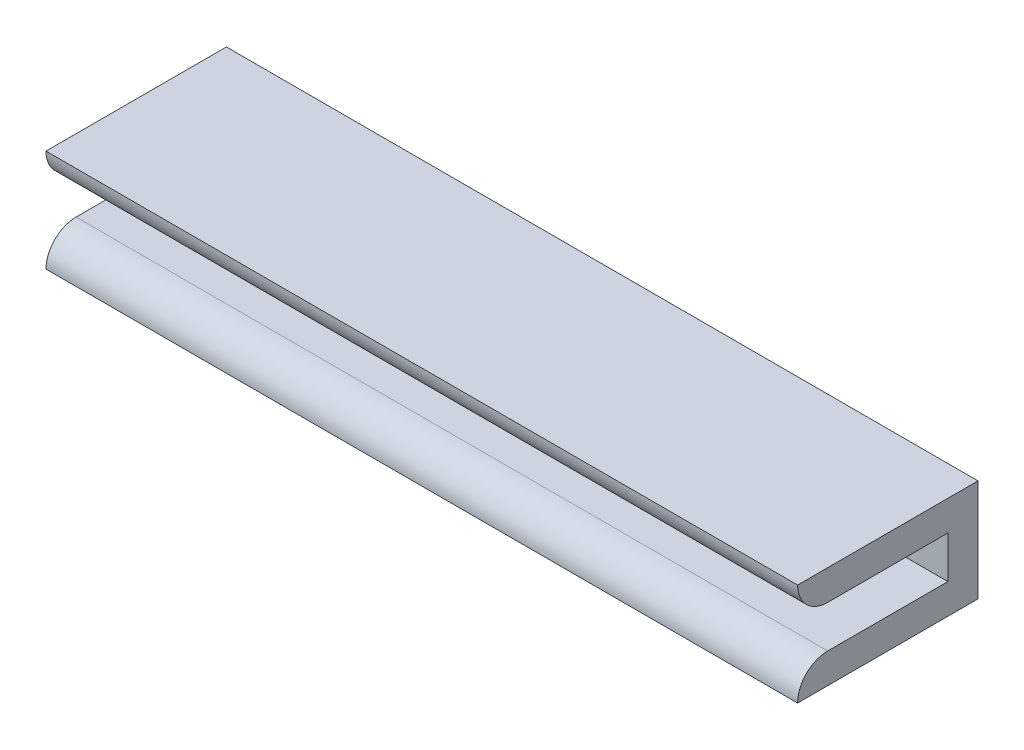
SolidWorks part; units mm, degrees
ref_plane "前视基准面" through (0, 0, 0) normal (0, 0, 1) x (1, 0, 0)
ref_plane "上视基准面" through (0, 0, 0) normal (0, 1, 0) x (1, 0, 0)
ref_plane "右视基准面" through (0, 0, 0) normal (1, 0, 0) x (0, 0, -1)
sketch "草图1" plane through (0, 0, 0) normal (0, 0, 1) x (1, 0, 0)
  line L1 (0, 0) -> (50, 0)
  line L2 (0, 0) -> (0, 2)
  line L3 (0, 2) -> (50, 2)
  line L4 (50, 0) -> (50, 2)
  line L5 (0, -2.8) -> (50, -2.8)
  line L6 (0, -2.8) -> (0, -4.8)
  line L7 (0, -4.8) -> (50, -4.8)
  line L8 (50, -2.8) -> (50, -4.8)
  dimension "D1" = 2
  dimension "D2" = 2
  dimension "D3" = 2.8
  dimension "D4" = 50
extrude "凸台-拉伸1" add sketch "草图1" along normal blind 10
sketch "草图2" plane through (0, 0, 0) normal (0, 0, -1) x (-1, 0, 0)
  line L1 (-50, 2) -> (0, 2)
  line L2 (-50, 2) -> (-50, -4.8)
  line L3 (-50, -4.8) -> (0, -4.8)
  line L4 (0, 2) -> (0, -4.8)
extrude "凸台-拉伸2" add sketch "草图2" along normal blind 2
fillet "圆角1" radius 2 2 edges at (25, -2.8, 10) (25, 0, 10)
